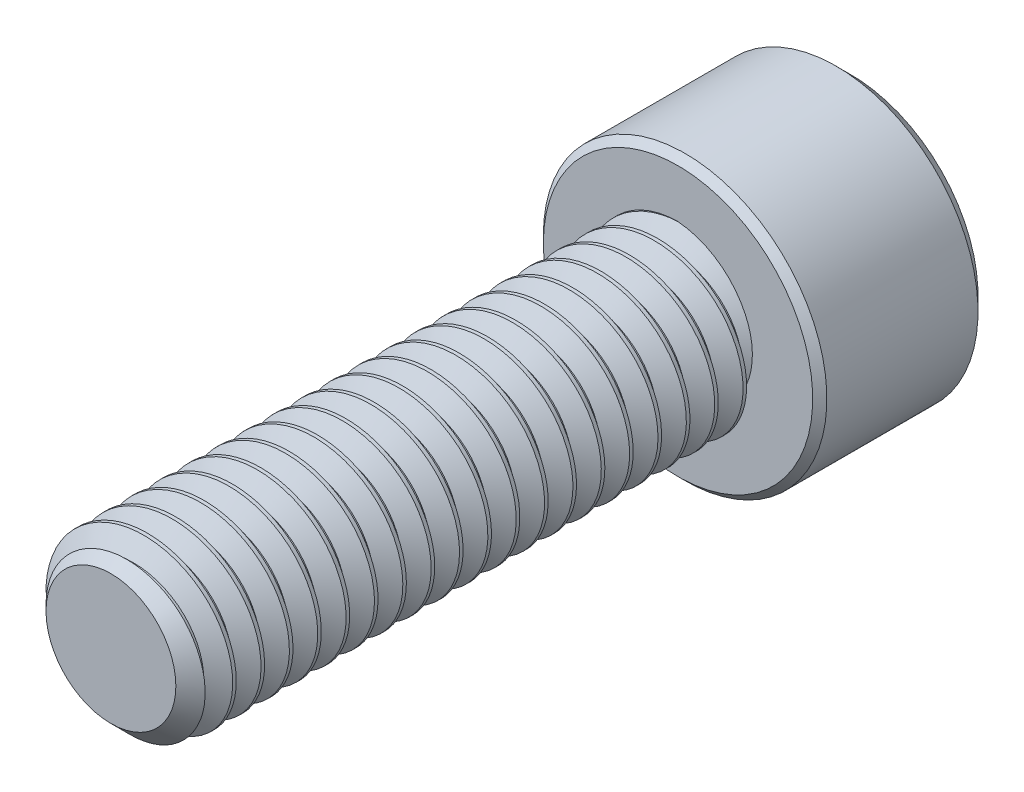
SolidWorks part; units mm, degrees
ref_plane "Front Plane" through (0, 0, 0) normal (0, 0, 1) x (1, 0, 0)
ref_plane "Top Plane" through (0, 0, 0) normal (0, 1, 0) x (1, 0, 0)
ref_plane "Right Plane" through (0, 0, 0) normal (1, 0, 0) x (0, 0, -1)
sketch "Sketch0" plane through (0, 0, 0) normal (1, 0, 0) x (0, 0, -1)
  line L0 (0, 0) -> (15.875, 0) construction
  point P2 (20.701, 0)
  point P4 (0, 0)
  dimension "D1" = 15.875
  dimension "D2" = 4.826
  dimension "Min Thread" = 0
sketch "Sketch1" plane through (0, 0, 0) normal (0, 0, 1) x (1, 0, 0)
  circle A0 centre (0, 0) radius 2.413
  dimension "OD" = 4.826
extrude "Extrude1" add sketch "Sketch1" against normal blind 15.875
sketch "Sketch2" plane through (0, 0, 0) normal (0, 0, 1) x (1, 0, 0)
  circle A0 centre (0, 0) radius 2.413 construction
  circle A1 centre (0, 0) radius 2.413
curve "Helix/Spiral1" pitch 0.7937 height 16.6687 turns 21 parameters "pitch"=0.7937
chamfer "Chamfer3" distance 0.5953 angle 45 1 edges at (2.413, 0, 0)
sketch "Sketch3" plane through (0, 0, 0) normal (1, 0, 0) x (0, 0, -1)
  line L0 (-0.6945, 2.413) -> (-0.3969, 1.8974)
  line L1 (-0.3969, 1.8974) -> (-0.2977, 1.8974)
  line L2 (-0.2977, 1.8974) -> (0, 2.413)
  line L3 (-0.6945, 2.413) -> (0, 2.413)
  line L4 (-0.3473, 2.413) -> (-0.3473, 1.8974) construction
  line L5 (-0.5457, 2.1552) -> (-0.1488, 2.1552) construction
  line L6 (0, 2.413) -> (0, -2.413) construction
  dimension "D1" = 0.0992
  dimension "D2" = 0.3969
  dimension "D3" = 60
sweep "Cut-Sweep1" cut profiles "Sketch3" path "Helix/Spiral1"
sketch "Sketch5" plane through (0, 0, 0) normal (1, 0, 0) x (0, 0, -1)
  line L0 (15.875, -1.9083) -> (15.875, 1.7217) construction
  line L1 (15.875, 2.413) -> (0, 2.413)
  line L2 (15.875, 2.413) -> (15.875, 0)
  line L3 (15.875, 0) -> (-0.8783, 0)
  line L4 (0, 0) -> (15.875, 0) construction
  line L5 (0, 2.413) -> (-0.8783, 0)
  line L6 (0, 0) -> (18.415, 0) construction
  dimension "D1" = 70
  dimension "D3" = 2.54
revolve "partially thread" [suppressed] add sketch "Sketch5" angle 360 about L6
sketch "Sketch6" plane through (0, 0, -15.875) normal (0, 0, -1) x (-1, 0, 0)
  circle A0 centre (0, 0) radius 3.9688
  dimension "head dia" = 7.9375
extrude "Extrude2" add sketch "Sketch6" along normal blind 4.826
sketch "Sketch7" plane through (0, 0, -20.701) normal (0, 0, -1) x (-1, 0, 0)
  line L1 (0, 2.2914) -> (-1.9844, 1.1457)
  line L2 (-1.9844, 1.1457) -> (-1.9844, -1.1457)
  line L3 (-1.9844, -1.1457) -> (0, -2.2914)
  line L4 (0, -2.2914) -> (1.9844, -1.1457)
  line L5 (1.9844, -1.1457) -> (1.9844, 1.1457)
  line L6 (1.9844, 1.1457) -> (0, 2.2914)
  circle A0 centre (0, 0) radius 1.9844 construction
  dimension "hex dia" = 3.9688
extrude "Cut-Extrude1" cut sketch "Sketch7" against normal blind 2.9766
sketch "Sketch8" plane through (0, 0, -20.701) normal (0, 0, -1) x (-1, 0, 0)
  circle A0 centre (0, 0) radius 2.2914
extrude "Cut-Extrude2" cut sketch "Sketch8" against normal through all draft 45
chamfer "Chamfer1" distance 0.3969 angle 45 1 edges at (-3.9688, 0, -20.701)
chamfer "Chamfer2" distance 0.1984 angle 45 1 edges at (-3.9688, 0, -15.875)
sketch "Sketch9" plane through (0, 0, 0) normal (1, 0, 0) x (0, 0, -1)
  line L0 (0, 2.413) -> (0, -2.413) construction
  line L1 (1.9844, 2.413) -> (1.9844, -2.413) construction
  line L2 (20.701, 3.9688) -> (20.701, -3.9688) construction
  line L3 (15.875, 3.9688) -> (15.875, -3.9688) construction
  line L4 (15.875, 3.7703) -> (15.875, -3.7703) construction
  line L5 (20.701, -3.5719) -> (20.701, 3.5719) construction
  line L6 (15.875, -3.9688) -> (15.875, 3.9688) construction
  line L7 (0, 1.8177) -> (0, -1.8177) construction
  line L8 (-0.6945, 2.413) -> (0, 2.413) construction
  line L9 (1.9844, 0) -> (0, 0) construction
  dimension "D1" = 1.9844
equation "\"D3@Helix/Spiral1\" = \"screw length@Extrude1\"+\"pitch@Helix/Spiral1\""
equation "\"D1@Sketch3\" = \"pitch@Helix/Spiral1\"*.125"
equation "\"D2@Sketch3\" = \"pitch@Helix/Spiral1\"*.5"
equation "\"D1@Cut-Extrude1\" = \"hex dia@Sketch7\"*.75"
equation "\"D1@Chamfer1\" = \"head dia@Sketch6\"*.05"
equation "\"D1@Sketch9\" = \"pitch@Helix/Spiral1\"*2.50"
equation "\"D1@Chamfer2\" = \"D1@Chamfer1\"/2"
equation "\"D1@Chamfer3\" = \"pitch@Helix/Spiral1\"*.750"
equation "\"D1@Sketch0\" = \"screw length@Extrude1\""
equation "\"D2@Sketch0\" = \"head depth@Extrude2\""
